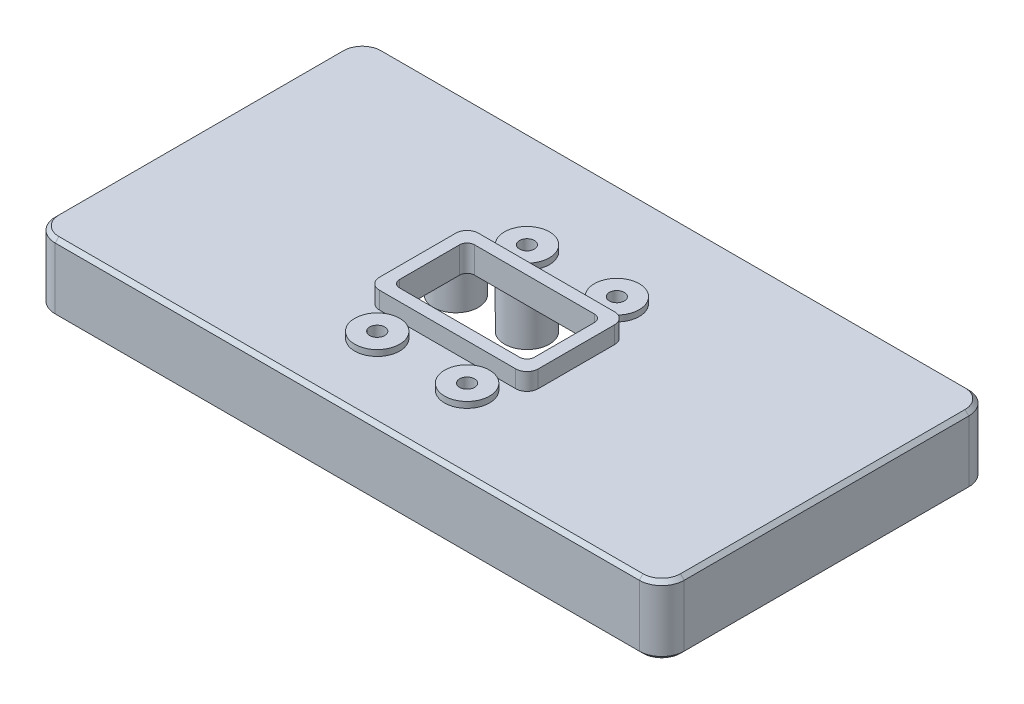
SolidWorks part; units mm, degrees
ref_plane "Front Plane" through (0, 0, 0) normal (0, 0, 1) x (1, 0, 0)
ref_plane "Top Plane" through (0, 0, 0) normal (0, 1, 0) x (1, 0, 0)
ref_plane "Right Plane" through (0, 0, 0) normal (1, 0, 0) x (0, 0, -1)
sketch "Sketch1" plane through (0, 0, 0) normal (0, 1, 0) x (1, 0, 0)
  line L0 (-39, -36) -> (39, -36)
  line L1 (42, -39) -> (42, -77)
  line L2 (39, -80) -> (-39, -80)
  line L3 (-42, -77) -> (-42, -39)
  arc A0 (-42, -39) -> (-39, -36) centre (-39, -39) cw
  arc A1 (39, -36) -> (42, -39) centre (39, -39) cw
  arc A2 (42, -77) -> (39, -80) centre (39, -77) cw
  arc A3 (-39, -80) -> (-42, -77) centre (-39, -77) cw
extrude "Boss-Extrude1" add sketch "Sketch1" along normal blind 9.2 from offset 50
chamfer "Chamfer1" distance 0.5 angle 45 8 edges at (0, 50, 36) (-41.1213, 50, 36.8787) (41.1213, 50, 36.8787) (-42, 50, 58) (42, 50, 58) (-41.1213, 50, 79.1213) (41.1213, 50, 79.1213) (0, 50, 80)
chamfer "Chamfer2" distance 0.5 angle 45 8 edges at (0, 59.2, 36) (-41.1213, 59.2, 36.8787) (41.1213, 59.2, 36.8787) (-42, 59.2, 58) (42, 59.2, 58) (-41.1213, 59.2, 79.1213) (41.1213, 59.2, 79.1213) (0, 59.2, 80)
sketch "Sketch2" plane through (0, 0, 0) normal (0, 1, 0) x (1, 0, 0)
  line L0 (-38.6, -38.4) -> (38.6, -38.4)
  line L1 (39.6, -39.4) -> (39.6, -76.6)
  line L2 (38.6, -77.6) -> (-38.6, -77.6)
  line L3 (-39.6, -76.6) -> (-39.6, -39.4)
  arc A0 (-39.6, -39.4) -> (-38.6, -38.4) centre (-38.6, -39.4) cw
  arc A1 (38.6, -38.4) -> (39.6, -39.4) centre (38.6, -39.4) cw
  arc A2 (39.6, -76.6) -> (38.6, -77.6) centre (38.6, -76.6) cw
  arc A3 (-38.6, -77.6) -> (-39.6, -76.6) centre (-38.6, -76.6) cw
extrude "Boss-Extrude2" add sketch "Sketch2" along normal blind 9 from offset 49 separate body
combine bodies "Combine1" operation type subtract main body 101 bodies to subtract 102
sketch "Sketch3" plane through (0, 0, 0) normal (0, 1, 0) x (1, 0, 0)
  circle A0 centre (-15, -50.5) radius 3
extrude "Boss-Extrude3" add sketch "Sketch3" along normal blind 8.01 from offset 50
sketch "Sketch4" plane through (0, 0, 0) normal (0, 1, 0) x (1, 0, 0)
  circle A0 centre (-15, -50.5) radius 1
extrude "Boss-Extrude4" add sketch "Sketch4" along normal blind 9.4 from offset 49 separate body
combine bodies "Combine2" operation type subtract main body 104 bodies to subtract 105
sketch "Sketch5" plane through (0, 0, 0) normal (0, 1, 0) x (1, 0, 0)
  circle A0 centre (-15, -69.5) radius 3
extrude "Boss-Extrude5" add sketch "Sketch5" along normal blind 8.01 from offset 50
sketch "Sketch6" plane through (0, 0, 0) normal (0, 1, 0) x (1, 0, 0)
  circle A0 centre (-15, -69.5) radius 1
extrude "Boss-Extrude6" add sketch "Sketch6" along normal blind 9.4 from offset 49 separate body
combine bodies "Combine3" operation type subtract main body 107 bodies to subtract 108
sketch "Sketch7" plane through (0, 0, 0) normal (0, 1, 0) x (1, 0, 0)
  circle A0 centre (15, -50.5) radius 3
extrude "Boss-Extrude7" add sketch "Sketch7" along normal blind 8.01 from offset 50
sketch "Sketch8" plane through (0, 0, 0) normal (0, 1, 0) x (1, 0, 0)
  circle A0 centre (15, -50.5) radius 1
extrude "Boss-Extrude8" add sketch "Sketch8" along normal blind 9.4 from offset 49 separate body
combine bodies "Combine4" operation type subtract main body 110 bodies to subtract 111
sketch "Sketch9" plane through (0, 0, 0) normal (0, 1, 0) x (1, 0, 0)
  circle A0 centre (15, -69.5) radius 3
extrude "Boss-Extrude9" add sketch "Sketch9" along normal blind 8.01 from offset 50
sketch "Sketch10" plane through (0, 0, 0) normal (0, 1, 0) x (1, 0, 0)
  circle A0 centre (15, -69.5) radius 1
extrude "Boss-Extrude10" add sketch "Sketch10" along normal blind 9.4 from offset 49 separate body
combine bodies "Combine5" operation type subtract main body 113 bodies to subtract 114
sketch "Sketch11" plane through (0, 0, 0) normal (0, 1, 0) x (1, 0, 0)
  circle A0 centre (-6, -50) radius 3
extrude "Boss-Extrude11" add sketch "Sketch11" along normal blind 10 from offset 50
sketch "Sketch12" plane through (0, 0, 0) normal (0, 1, 0) x (1, 0, 0)
  circle A0 centre (-6, -50) radius 1
extrude "Boss-Extrude12" add sketch "Sketch12" along normal blind 9.5 from offset 51.5 separate body
combine bodies "Combine6" operation type subtract main body 116 bodies to subtract 117
sketch "Sketch13" plane through (0, 0, 0) normal (0, 1, 0) x (1, 0, 0)
  circle A0 centre (-6, -70) radius 3
extrude "Boss-Extrude13" add sketch "Sketch13" along normal blind 10 from offset 50
sketch "Sketch14" plane through (0, 0, 0) normal (0, 1, 0) x (1, 0, 0)
  circle A0 centre (-6, -70) radius 1
extrude "Boss-Extrude14" add sketch "Sketch14" along normal blind 9.5 from offset 51.5 separate body
combine bodies "Combine7" operation type subtract main body 119 bodies to subtract 120
sketch "Sketch15" plane through (0, 0, 0) normal (0, 1, 0) x (1, 0, 0)
  circle A0 centre (6, -50) radius 3
extrude "Boss-Extrude15" add sketch "Sketch15" along normal blind 10 from offset 50
sketch "Sketch16" plane through (0, 0, 0) normal (0, 1, 0) x (1, 0, 0)
  circle A0 centre (6, -50) radius 1
extrude "Boss-Extrude16" add sketch "Sketch16" along normal blind 9.5 from offset 51.5 separate body
combine bodies "Combine8" operation type subtract main body 122 bodies to subtract 123
sketch "Sketch17" plane through (0, 0, 0) normal (0, 1, 0) x (1, 0, 0)
  circle A0 centre (6, -70) radius 3
extrude "Boss-Extrude17" add sketch "Sketch17" along normal blind 10 from offset 50
sketch "Sketch18" plane through (0, 0, 0) normal (0, 1, 0) x (1, 0, 0)
  circle A0 centre (6, -70) radius 1
extrude "Boss-Extrude18" add sketch "Sketch18" along normal blind 9.5 from offset 51.5 separate body
combine bodies "Combine9" operation type subtract main body 125 bodies to subtract 126
sketch "Sketch19" plane through (0, 0, 0) normal (0, 1, 0) x (1, 0, 0)
  line L0 (-38.59, -38.39) -> (38.59, -38.39)
  line L1 (39.59, -39.39) -> (39.59, -76.61)
  line L2 (38.59, -77.61) -> (-38.59, -77.61)
  line L3 (-39.59, -76.61) -> (-39.59, -39.39)
  line L4 (-33.6, -39.6) -> (33.6, -39.6)
  line L5 (34.6, -40.6) -> (34.6, -71.6)
  line L6 (33.6, -72.6) -> (-33.6, -72.6)
  line L7 (-34.6, -71.6) -> (-34.6, -40.6)
  arc A0 (-39.59, -39.39) -> (-38.59, -38.39) centre (-38.59, -39.39) cw
  arc A1 (38.59, -38.39) -> (39.59, -39.39) centre (38.59, -39.39) cw
  arc A2 (39.59, -76.61) -> (38.59, -77.61) centre (38.59, -76.61) cw
  arc A3 (-38.59, -77.61) -> (-39.59, -76.61) centre (-38.59, -76.61) cw
  arc A4 (-34.6, -40.6) -> (-33.6, -39.6) centre (-33.6, -40.6) cw
  arc A5 (33.6, -39.6) -> (34.6, -40.6) centre (33.6, -40.6) cw
  arc A6 (34.6, -71.6) -> (33.6, -72.6) centre (33.6, -71.6) cw
  arc A7 (-33.6, -72.6) -> (-34.6, -71.6) centre (-33.6, -71.6) cw
extrude "Boss-Extrude19" add sketch "Sketch19" along normal blind 1.2 from offset 50
sketch "Sketch20" plane through (0, 0, 0) normal (0, 1, 0) x (1, 0, 0)
  line L0 (-9.1, -53.4) -> (9.1, -53.4)
  line L1 (10.6, -54.9) -> (10.6, -65.1)
  line L2 (9.1, -66.6) -> (-9.1, -66.6)
  line L3 (-10.6, -65.1) -> (-10.6, -54.9)
  arc A0 (-10.6, -54.9) -> (-9.1, -53.4) centre (-9.1, -54.9) cw
  arc A1 (9.1, -53.4) -> (10.6, -54.9) centre (9.1, -54.9) cw
  arc A2 (10.6, -65.1) -> (9.1, -66.6) centre (9.1, -65.1) cw
  arc A3 (-9.1, -66.6) -> (-10.6, -65.1) centre (-9.1, -65.1) cw
extrude "Boss-Extrude20" add sketch "Sketch20" along normal blind 3.51 from offset 57.99
sketch "Sketch21" plane through (0, 0, 0) normal (0, 1, 0) x (1, 0, 0)
  line L0 (-8, -55) -> (8, -55)
  line L1 (9, -56) -> (9, -64)
  line L2 (8, -65) -> (-8, -65)
  line L3 (-9, -64) -> (-9, -56)
  arc A0 (-9, -56) -> (-8, -55) centre (-8, -56) cw
  arc A1 (8, -55) -> (9, -56) centre (8, -56) cw
  arc A2 (9, -64) -> (8, -65) centre (8, -64) cw
  arc A3 (-8, -65) -> (-9, -64) centre (-8, -64) cw
extrude "Boss-Extrude21" add sketch "Sketch21" along normal blind 13 from offset 49 separate body
combine bodies "Combine10" operation type subtract main body 129 bodies to subtract 130
